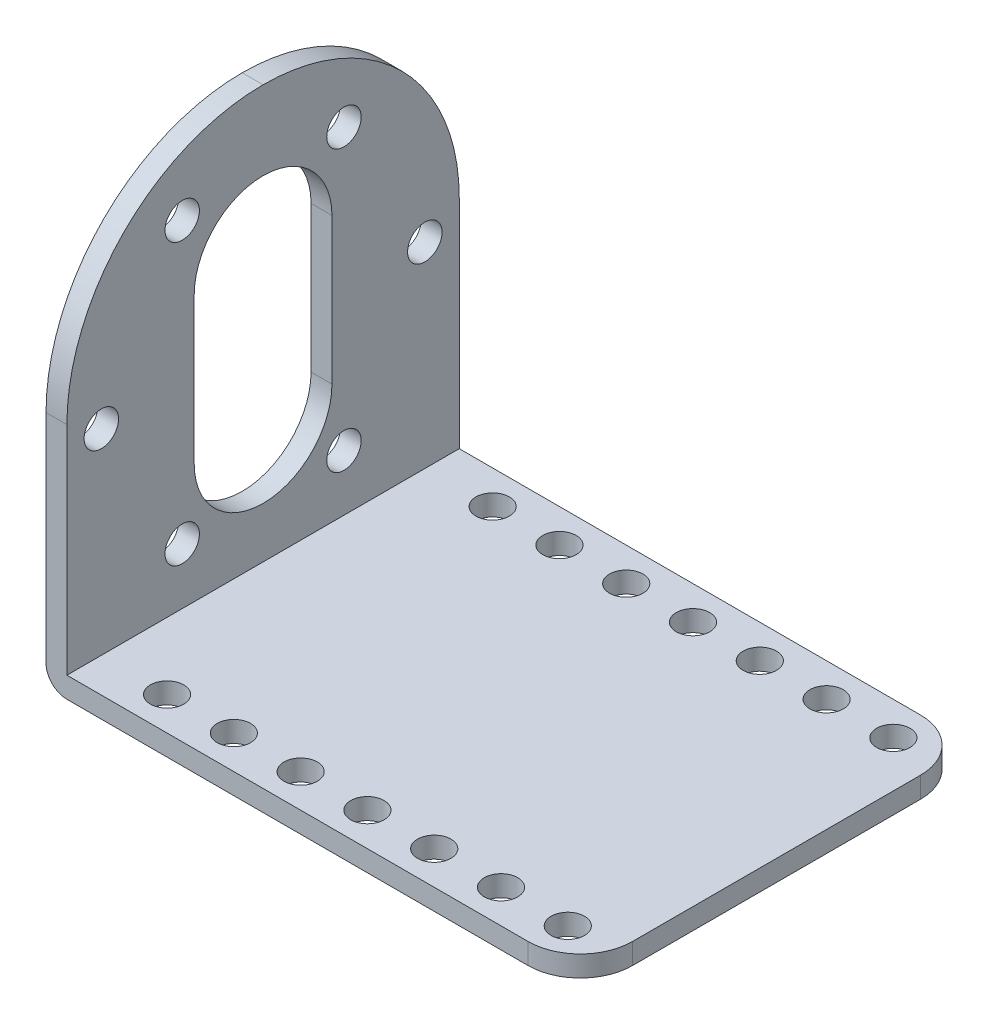
SolidWorks part; units mm, degrees
ref_plane "Front" through (0, 0, 0) normal (0, 0, 1) x (1, 0, 0)
ref_plane "Top" through (0, 0, 0) normal (0, 1, 0) x (1, 0, 0)
ref_plane "Right" through (0, 0, 0) normal (1, 0, 0) x (0, 0, -1)
sketch "Sketch1" plane through (0, 0, 0) normal (0, 1, 0) x (1, 0, 0)
  line L0 (-25.6, 0) -> (25.6, 0) construction
  line L1 (-25.6, 18.8) -> (25.6, 18.8)
  line L2 (-25.6, 18.8) -> (-25.6, -18.8)
  line L3 (-25.6, -18.8) -> (25.6, -18.8)
  line L4 (25.6, 18.8) -> (25.6, -18.8)
  line L5 (-25.6, 18.8) -> (25.6, -18.8) construction
  line L6 (-25.6, -18.8) -> (25.6, 18.8) construction
  line L7 (0, 18.8) -> (0, -18.8) construction
  circle A0 centre (-17.2, 15.6) radius 1.6
  circle A1 centre (-10.8, 15.6) radius 1.6
  circle A2 centre (-4.4, 15.6) radius 1.6
  circle A3 centre (2, 15.6) radius 1.6
  circle A4 centre (8.4, 15.6) radius 1.6
  circle A5 centre (14.8, 15.6) radius 1.6
  circle A6 centre (21.2, 15.6) radius 1.6
  circle A7 centre (21.2, -15.6) radius 1.6
  circle A8 centre (14.8, -15.6) radius 1.6
  circle A9 centre (8.4, -15.6) radius 1.6
  circle A10 centre (2, -15.6) radius 1.6
  circle A11 centre (-4.4, -15.6) radius 1.6
  circle A12 centre (-10.8, -15.6) radius 1.6
  circle A13 centre (-17.2, -15.6) radius 1.6
  point P0 (0, 0)
  point P38 (0, 0)
  dimension "D3" = 3.2
  dimension "D5" = 31.2
  dimension "D6" = 8.4
  dimension "D1" = 51.2
  dimension "D2" = 37.6
  dimension "D4" = 7
extrude "Boss-Extrude1" add sketch "Sketch1" along normal blind 2
fillet "Fillet2" radius 5 2 edges at (25.6, 1, 18.8) (25.6, 1, -18.8)
sketch "Sketch2" plane through (0, 2, 0) normal (0, 1, 0) x (1, 0, 0)
  line L0 (-25.6, -18.8) -> (20.6, -18.8) construction
  line L1 (-25.6, 18.8) -> (-23.6, 18.8)
  line L2 (-25.6, 18.8) -> (-25.6, -18.8)
  line L3 (-25.6, -18.8) -> (-23.6, -18.8)
  line L4 (-23.6, 18.8) -> (-23.6, -18.8)
  dimension "D1" = 2
extrude "Boss-Extrude2" add sketch "Sketch2" along normal blind 39.6
sketch "Sketch3" plane through (-25.6, 0, 0) normal (-1, 0, 0) x (0, 0, 1)
  line L0 (0, 41.6) -> (0, 0) construction
  line L1 (-18.8, 41.6) -> (18.8, 41.6) construction
  line L2 (-18.8, 0) -> (18.8, 0) construction
  line L3 (0, 27.4561) -> (0, 13.4561) construction
  line L4 (6.6, 27.4561) -> (6.6, 13.4561)
  line L5 (-6.6, 27.4561) -> (-6.6, 13.4561)
  circle A0 centre (0, 20.8) radius 15.5 construction
  circle A1 centre (15.5, 20.8) radius 1.65
  circle A2 centre (7.75, 7.3766) radius 1.65
  circle A3 centre (-7.75, 7.3766) radius 1.65
  circle A4 centre (-15.5, 20.8) radius 1.65
  circle A5 centre (-7.75, 34.2234) radius 1.65
  circle A6 centre (7.75, 34.2234) radius 1.65
  arc A7 (6.6, 27.4561) -> (-6.6, 27.4561) centre (0, 27.4561) ccw
  arc A8 (-6.6, 13.4561) -> (6.6, 13.4561) centre (0, 13.4561) ccw
  point P21 (0, 21.6412)
  point P24 (0, 20.8)
  point P25 (0, 20.4561)
  dimension "D1" = 31
  dimension "D2" = 3.3
  dimension "D4" = 20.8
  dimension "D5" = 14
  dimension "D6" = 13.2
  dimension "D3" = 6
extrude "Cut-Extrude1" cut sketch "Sketch3" against normal up to next contours A6 | A1 | A2 | A3 | A4 | A5 | L5 A8 L4 A7 region at (-25.6, 20.4561, 0) region at (-25.6, 20.8, 15.5) region at (-25.6, 7.3766, 7.75) region at (-25.6, 7.3766, -7.75) region at (-25.6, 20.8, -15.5) region at (-25.6, 34.2234, -7.75) region at (-25.6, 34.2234, 7.75)
fillet "Fillet3" radius 18.8 2 edges at (-24.6, 41.6, -18.8) (-24.6, 41.6, 18.8)
fillet "Fillet4" radius 2 1 edges at (-25.6, 0, 0)
